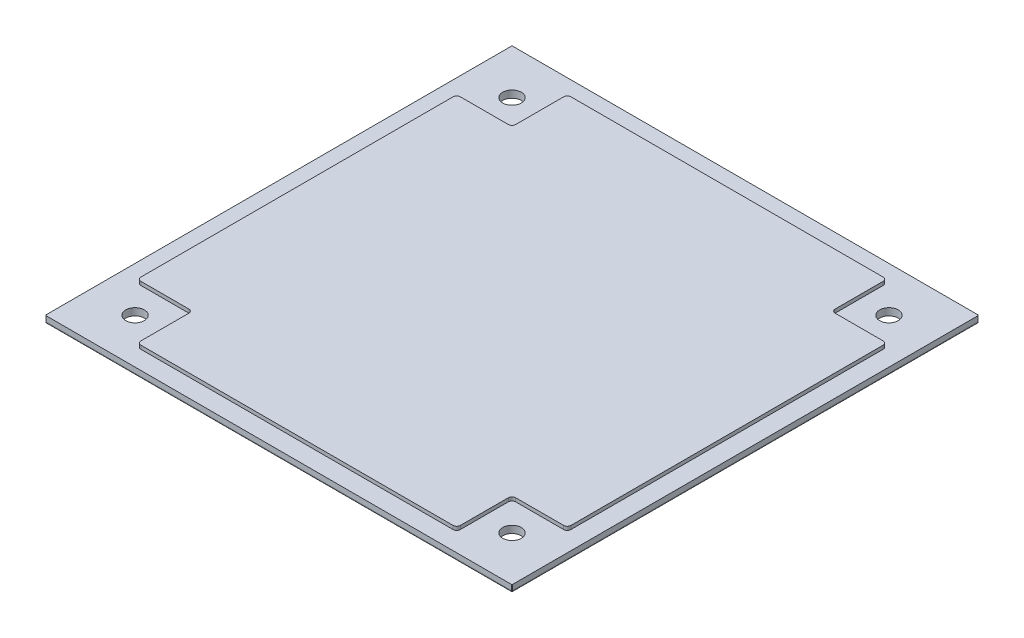
SolidWorks part; units mm, degrees
ref_plane "Front Plane" through (0, 0, 0) normal (0, 0, 1) x (1, 0, 0)
ref_plane "Top Plane" through (0, 0, 0) normal (0, 1, 0) x (1, 0, 0)
ref_plane "Right Plane" through (0, 0, 0) normal (1, 0, 0) x (0, 0, -1)
other "Configuration Table"
sketch "草图1" plane through (0, 0, 0) normal (0, 1, 0) x (1, 0, 0)
  line L1 (-65, 65) -> (65, 65)
  line L2 (-65, 65) -> (-65, -65)
  line L3 (-65, -65) -> (65, -65)
  line L4 (65, 65) -> (65, -65)
  line L5 (-65, 65) -> (65, -65) construction
  line L6 (-65, -65) -> (65, 65) construction
  point P0 (0, 0)
extrude "凸台-拉伸1" add sketch "草图1" along normal blind 3
sketch "草图2" plane through (0, 3, 0) normal (0, 1, 0) x (1, 0, 0)
  line L0 (52.5, 65) -> (52.5, 52.5) construction
  line L1 (65, 65) -> (-65, 65) construction
  line L2 (52.5, 52.5) -> (65, 52.5) construction
  line L3 (65, -65) -> (65, 65) construction
  line L4 (65, 52.5) -> (65, 65) construction
  line L5 (65, 65) -> (52.5, 65) construction
  circle A0 centre (52.5, 52.5) radius 2.6
  circle A1 centre (52.5, -52.5) radius 2.6
  circle A2 centre (-52.5, -52.5) radius 2.6
  circle A3 centre (-52.5, 52.5) radius 2.6
  point P19 (0, 0)
  dimension "D1" = 4
extrude "切除-拉伸1" cut sketch "草图2" against normal through all
sketch "草图4" plane through (0, 3, 0) normal (0, 1, 0) x (1, 0, 0)
  line L0 (65, 65) -> (44.5, 65)
  line L1 (44.5, 65) -> (44.5, 44.5)
  line L2 (44.5, 44.5) -> (65, 44.5)
  line L3 (65, -65) -> (65, 65) construction
  line L4 (65, 44.5) -> (65, 65)
  line L5 (65, -44.5) -> (44.5, -44.5)
  line L6 (44.5, -44.5) -> (44.5, -65)
  line L7 (44.5, -65) -> (65, -65)
  line L8 (65, -65) -> (65, -44.5)
  line L9 (-44.5, -65) -> (-44.5, -44.5)
  line L10 (-44.5, -44.5) -> (-65, -44.5)
  line L11 (-65, -44.5) -> (-65, -65)
  line L12 (-65, -65) -> (-44.5, -65)
  line L13 (-65, 44.5) -> (-44.5, 44.5)
  line L14 (-44.5, 44.5) -> (-44.5, 65)
  line L15 (-44.5, 65) -> (-65, 65)
  line L16 (-65, 65) -> (-65, 44.5)
  point P22 (0, 0)
  dimension "D1" = 4
extrude "切除-拉伸2" cut sketch "草图4" against normal blind 1
sketch "草图5" plane through (0, 3, 0) normal (0, 1, 0) x (1, 0, 0)
  line L5 (-44.5, 65) -> (44.5, 65)
  line L6 (44.5, 65) -> (44.5, 59.9)
  line L7 (44.5, 65) -> (44.5, 44.5) construction
  line L8 (-44.5, 65) -> (-44.5, 59.9)
  line L9 (-44.5, 44.5) -> (-44.5, 65) construction
  line L10 (-44.5, 59.9) -> (44.5, 59.9)
  line L11 (65, 44.5) -> (65, -44.5)
  line L12 (65, -44.5) -> (59.9, -44.5)
  line L13 (65, 44.5) -> (59.9, 44.5)
  line L14 (59.9, 44.5) -> (59.9, -44.5)
  line L15 (44.5, -65) -> (-44.5, -65)
  line L16 (-44.5, -65) -> (-44.5, -59.9)
  line L17 (44.5, -65) -> (44.5, -59.9)
  line L18 (44.5, -59.9) -> (-44.5, -59.9)
  line L19 (-65, -44.5) -> (-65, 44.5)
  line L20 (-65, 44.5) -> (-59.9, 44.5)
  line L21 (-65, -44.5) -> (-59.9, -44.5)
  line L22 (-59.9, -44.5) -> (-59.9, 44.5)
  point P27 (0, 0)
  dimension "D1" = 4
extrude "切除-拉伸3" cut sketch "草图5" against normal up to surface (1 mm away) up to face at (-54.75, 2, 54.75)
chamfer "倒角1" distance 0.2 angle 45 4 edges at (-65, 1, 65) (-65, 1, -65) (65, 1, -65) (65, 1, 65)
chamfer "倒角2" [suppressed] distance 1 angle 45
fillet "圆角1" radius 0.5 4 edges at (-65, 0, 0) (0, 0, 65) (65, 0, 0) (0, 0, -65)
fillet "圆角2" radius 1 12 edges at (44.5, 2.5, -59.9) (44.5, 2.5, -44.5) (59.9, 2.5, -44.5) (59.9, 2.5, 44.5) (44.5, 2.5, 44.5) (44.5, 2.5, 59.9) (-44.5, 2.5, 59.9) (-44.5, 2.5, 44.5) (-59.9, 2.5, 44.5) (-59.9, 2.5, -44.5) (-44.5, 2.5, -44.5) (-44.5, 2.5, -59.9)
